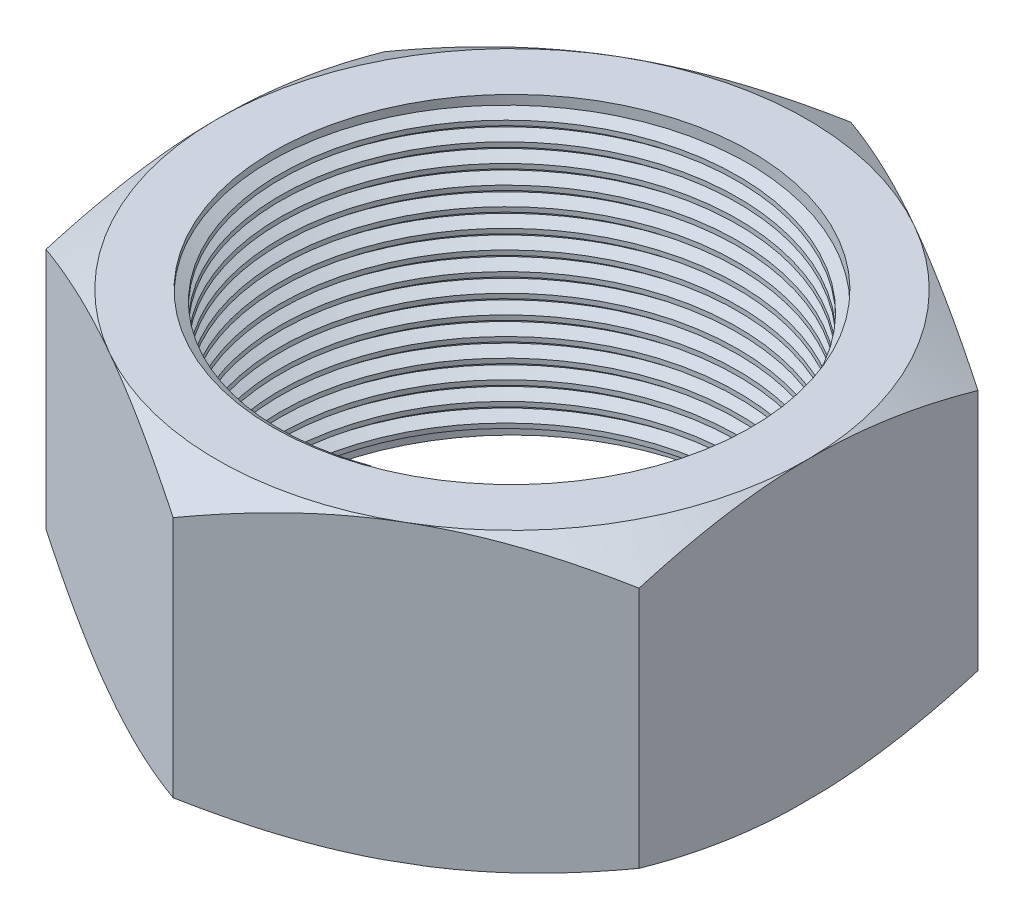
SolidWorks part; units mm, degrees
material "Stal nierdzewna (ferrytyczna)"
ref_plane "Front Plane" through (0, 0, 0) normal (0, 0, 1) x (1, 0, 0)
ref_plane "Top Plane" through (0, 0, 0) normal (0, 1, 0) x (1, 0, 0)
ref_plane "Right Plane" through (0, 0, 0) normal (1, 0, 0) x (0, 0, -1)
sketch "Szkic1" plane through (0, 0, 0) normal (0, 1, 0) x (1, 0, 0)
  line L1 (4.9849, 2.9127) -> (-0.03, 5.7734)
  line L2 (-0.03, 5.7734) -> (-5.0149, 2.8607)
  line L3 (-5.0149, 2.8607) -> (-4.9849, -2.9127)
  line L4 (-4.9849, -2.9127) -> (0.03, -5.7734)
  line L5 (0.03, -5.7734) -> (5.0149, -2.8607)
  line L6 (5.0149, -2.8607) -> (4.9849, 2.9127)
  circle A0 centre (0, 0) radius 5 construction
extrude "Dodanie-wyciągnięcie1" add sketch "Szkic1" along normal blind 5 contours L6 L1 L2 L3 L4 L5
sketch "Szkic3" plane through (0, 5, 0) normal (0, 1, 0) x (1, 0, 0)
  circle A0 centre (0, 0) radius 4.05
extrude "Wytnij-wyciągnięcie1" cut sketch "Szkic3" against normal blind 10
thread "Gwint1" pitch 0.3175 method extrude profile "Profil gwintu1" start angle 0, offset 0, length 4.7, pitch 0.3175, diameter 8.1
ref_plane "Płaszczyzna1" through (4.05, 0, 0) normal (0, 0, 1) x (1, 0, 0)
sketch "Profil gwintu1" plane through (4.05, 0, 0) normal (0, 0, 1) x (1, 0, 0)
  line L0 (0, 0) -> (0, 0.3175) construction
  line L11 (0, 0) -> (0, 0.2778)
  line L12 (0, 0.2778) -> (-0.1719, 0.1786)
  line L13 (-0.1719, 0.1786) -> (-0.1719, 0.0992)
  line L15 (-0.1719, 0.0992) -> (0, 0)
  line L17 (-0.1719, 0.1389) -> (0, 0.1389) construction
  point P2 (0, 0)
  dimension "Pitch" = 0.3175
  dimension "Profile_Angle" = 60
  dimension "Profile_Land" = 0.0794
  dimension "Profile_Height" = 0.1719
sketch "Szkic6" plane through (0, 0, 0) normal (0, -1, 0) x (1, 0, 0)
  circle A0 centre (0, 0) radius 5.0084
extrude "Wytnij-wyciągnięcie2" cut sketch "Szkic6" against normal blind 10 draft 60 flip side to cut
sketch "Szkic9" plane through (0, 5, 0) normal (0, 1, 0) x (1, 0, 0)
  circle A0 centre (0, 0) radius 5
extrude "Wytnij-wyciągnięcie4" cut sketch "Szkic9" against normal blind 10 draft 60 flip side to cut
